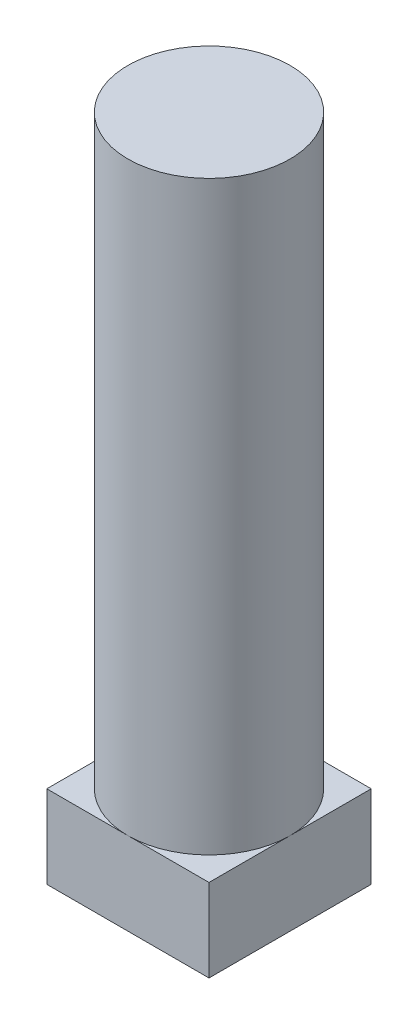
SolidWorks part; units mm, degrees
ref_plane "Front Plane" through (0, 0, 0) normal (0, 0, 1) x (1, 0, 0)
ref_plane "Top Plane" through (0, 0, 0) normal (0, 1, 0) x (1, 0, 0)
ref_plane "Right Plane" through (0, 0, 0) normal (1, 0, 0) x (0, 0, -1)
sketch "Sketch1" plane through (0, 0, 0) normal (0, 1, 0) x (1, 0, 0)
  line L1 (-2.45, -2.45) -> (2.45, -2.45)
  line L2 (-2.45, -2.45) -> (-2.45, 2.45)
  line L3 (-2.45, 2.45) -> (2.45, 2.45)
  line L4 (2.45, -2.45) -> (2.45, 2.45)
  line L5 (-2.45, -2.45) -> (2.45, 2.45) construction
  line L6 (-2.45, 2.45) -> (2.45, -2.45) construction
  point P0 (0, 0)
  dimension "D1" = 4.9
extrude "Boss-Extrude1" add sketch "Sketch1" along normal blind 2.5 contours L2 L3 L4 L1
sketch "Sketch2" plane through (0, 2.5, 0) normal (0, 1, 0) x (1, 0, 0)
  line L0 (2.45, -2.45) -> (2.45, 2.45) construction
  circle A0 centre (0, 0) radius 2.45
extrude "Boss-Extrude2" add sketch "Sketch2" along normal blind 17.7
equation "\"a\"= 1"
equation "\"b\"= 1"
equation "\"c\"= 1"
equation "\"d\"= 1"
equation "\"e\"= 1"
equation "\"x\"= 1"
equation "\"y\"= 1"
equation "\"z\"= 1"
